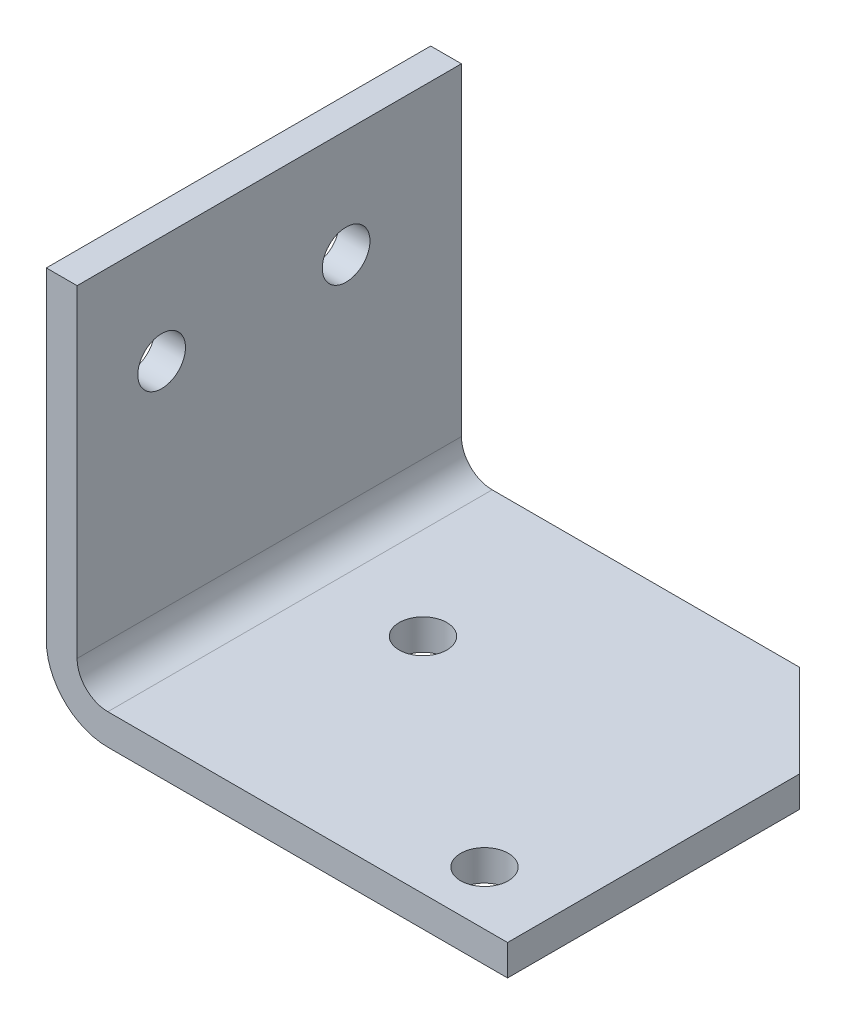
SolidWorks part; units mm, degrees
material "6061 Alloy"
ref_plane "Спереди" through (0, 0, 0) normal (0, 0, 1) x (1, 0, 0)
ref_plane "Сверху" through (0, 0, 0) normal (0, 1, 0) x (1, 0, 0)
ref_plane "Справа" through (0, 0, 0) normal (1, 0, 0) x (0, 0, -1)
sketch "Sketch1" plane through (0, 0, 0) normal (0, 0, 1) x (1, 0, 0)
  line L0 (0, 0) -> (30, 0)
  line L1 (30, 0) -> (30, 2)
  line L2 (30, 2) -> (2, 2)
  line L3 (2, 2) -> (2, 25)
  line L4 (2, 25) -> (0, 25)
  line L5 (0, 25) -> (0, 0)
  dimension "D1" = 30
  dimension "D2" = 25
  dimension "D4" = 2
extrude "Base" add sketch "Sketch1" along normal blind 25
sketch "Sketch2" plane through (0, 0, 0) normal (-1, 0, 0) x (0, 0, 1)
  line L0 (25, 25) -> (25, 0) construction
  line L2 (25, 0) -> (0, 0) construction
  circle A0 centre (19.5, 18) radius 1.55
  circle A1 centre (7.5, 18) radius 1.55
  dimension "D5" = 3.1
  dimension "D1" = 12
  dimension "D2" = 5.5
  dimension "D3" = 18
extrude "AcrylicSide" cut sketch "Sketch2" against normal up to surface (2 mm away) up to face at (2, 13.5, 12.5)
sketch "Sketch4" plane through (0, 0, 0) normal (0, -1, 0) x (1, 0, 0)
  line L0 (0, 25) -> (0, 0) construction
  line L1 (0, 0) -> (30, 0) construction
  circle A0 centre (10, 10.5) radius 1.55
  circle A1 centre (25, 21.5) radius 1.55
  dimension "D5" = 3.1
  dimension "D6" = 3.1
  dimension "D1" = 21.5
  dimension "D2" = 10.5
  dimension "D3" = 10
  dimension "D4" = 15
extrude "CableChainSide" cut sketch "Sketch4" against normal through all
chamfer "Chamfer2" distance 6 angle 45 1 edges at (30, 1, 0)
fillet "Fillet1" radius 2 1 edges at (2, 2, 12.5)
fillet "Fillet2" radius 4 1 edges at (0, 0, 12.5)
